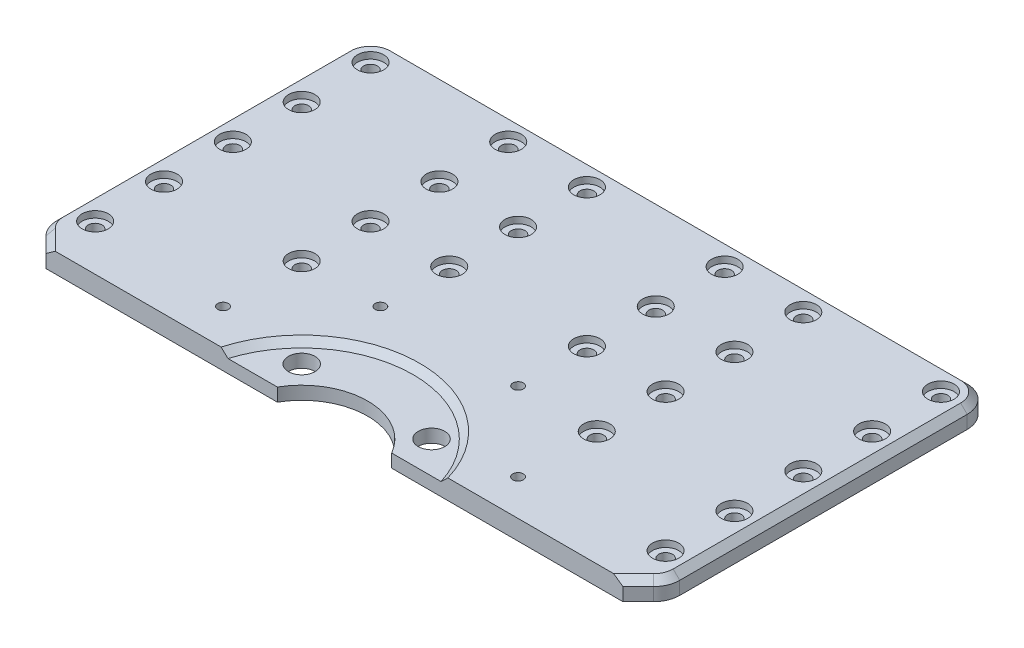
SolidWorks part; units mm, degrees
material "ABS"
ref_plane "正面" through (0, 0, 0) normal (0, 0, 1) x (1, 0, 0)
ref_plane "平面" through (0, 0, 0) normal (0, 1, 0) x (1, 0, 0)
ref_plane "右側面" through (0, 0, 0) normal (1, 0, 0) x (0, 0, -1)
sketch "ｽｹｯﾁ1" plane through (0, 0, 0) normal (0, 1, 0) x (1, 0, 0)
  line L0 (-10.05, 0) -> (-39, 0)
  line L1 (-39, 0) -> (-47.5, 8.5)
  line L2 (-47.5, 8.5) -> (-47.5, 58)
  line L3 (-47.5, 58) -> (47.5, 58)
  line L4 (47.5, 58) -> (47.5, 8.5)
  line L5 (47.5, 8.5) -> (39, 0)
  line L6 (39, 0) -> (10.05, 0)
  line L7 (-10.05, 0) -> (0, 0) construction
  line L8 (0, 0) -> (10.05, 0) construction
  arc A0 (10.05, 0) -> (-10.05, 0) centre (0, 0) ccw
  dimension "D1" = 20.1
  dimension "D2" = 95
  dimension "D3" = 58
  dimension "D4" = 78
extrude "ﾎﾞｽ - 押し出し1" add sketch "ｽｹｯﾁ1" along normal blind 3
hole_wizard "M2 なべ頭ねじ用座ぐり穴1" positions "ｽｹｯﾁ2" profile "ｽｹｯﾁ3" counterbore size "M2" standard "ISO"
sketch "ｽｹｯﾁ2" plane through (0, 3, 0) normal (0, 1, 0) x (1, 0, 0)
  line L0 (-43.5, 54) -> (-22.5, 54) construction
  line L2 (47.5, 58) -> (-47.5, 58) construction
  line L3 (-47.5, 58) -> (-47.5, 8.5) construction
  point P0 (-43.5, 54)
  point P2 (-22.5, 54)
  dimension "D1" = 4
  dimension "D2" = 4
  dimension "D3" = 21
sketch "ｽｹｯﾁ3" plane through (-43.5, 3, -54) normal (1, 0, 0) x (0, 0, 1)
  line L0 (0, 0) -> (0, 4.6309)
  line L1 (0, 4.6309) -> (1.05, 4)
  line L2 (1.05, 4) -> (1.05, 1)
  line L3 (1.05, 1) -> (2, 1)
  line L4 (2, 1) -> (2, 0)
  line L5 (2, 0) -> (0, 0)
  line L10 (0, 4.6309) -> (-1.05, 4) construction
  line L11 (0, -6.35) -> (0, 107.95) construction
  dimension "穴の直径" = 2.1
  dimension "穴の深さ" = 4
  dimension "座ぐり穴の直径" = 4
  dimension "座ぐり穴の深さ" = 1
  dimension "ﾄﾞﾘﾙ角度" = 118
pattern_linear "直線ﾊﾟﾀｰﾝ1" count 3 spacing 33 along (1, 0, 0) of "M2 なべ頭ねじ用座ぐり穴1"
pattern_linear "直線ﾊﾟﾀｰﾝ2" count 3 spacing 10.5 along (0, 0, 1) of "M2 なべ頭ねじ用座ぐり穴1", "直線ﾊﾟﾀｰﾝ1"
pattern_linear "直線ﾊﾟﾀｰﾝ3" count 2 spacing 31.5 along (0, 0, 1) of "M2 なべ頭ねじ用座ぐり穴1"
hole_wizard "M2 ねじ穴1" positions "ｽｹｯﾁ4" profile "ｽｹｯﾁ5" tap size "M2" standard "ISO"
sketch "ｽｹｯﾁ4" plane through (0, 3, 0) normal (0, 1, 0) x (1, 0, 0)
  line L0 (-22.5, 10.5) -> (-22.5, 22.5) construction
  line L1 (-22.5, 22.5) -> (-10.5, 22.5) construction
  line L2 (-10.5, 22.5) -> (-10.5, 33) construction
  line L4 (-39, 0) -> (-10.05, 0) construction
  point P0 (-10.5, 22.5)
  point P2 (-22.5, 10.5)
  dimension "D1" = 10.5
sketch "ｽｹｯﾁ5" plane through (-10.5, 3, -22.5) normal (1, 0, 0) x (0, 0, 1)
  line L0 (0, 0) -> (0, 6.4807)
  line L1 (0, 6.4807) -> (0.8, 6)
  line L2 (0.8, 6) -> (0.8, 0)
  line L5 (0.8, 0) -> (0, 0)
  line L10 (0, 6.4807) -> (-0.8, 6) construction
  line L11 (0, -6.35) -> (0, 107.95) construction
  dimension "ねじ下穴ﾄﾞﾘﾙ直径" = 1.6
  dimension "ねじ下穴ﾄﾞﾘﾙの深さ" = 6
  dimension "ﾄﾞﾘﾙ角度" = 118
cosmetic thread "穴のねじ山1" parameters "D1"=4, "D2"=2
cosmetic thread "穴のねじ山2" parameters "D1"=4, "D2"=2
hole_wizard "M2 なべ頭ねじ用座ぐり穴2" positions "ｽｹｯﾁ6" profile "ｽｹｯﾁ7" counterbore size "M2" standard "ISO"
sketch "ｽｹｯﾁ6" plane through (0, 3, 0) normal (0, 1, 0) x (1, 0, 0)
  line L0 (-43.5, 22.5) -> (-43.5, 12) construction
  line L3 (-43.5, 33) -> (-43.5, 22.5) construction
  point P0 (-43.5, 12)
sketch "ｽｹｯﾁ7" plane through (-43.5, 3, -12) normal (1, 0, 0) x (0, 0, 1)
  line L0 (0, 0) -> (0, 6.6309)
  line L1 (0, 6.6309) -> (1.05, 6)
  line L2 (1.05, 6) -> (1.05, 1)
  line L3 (1.05, 1) -> (2, 1)
  line L4 (2, 1) -> (2, 0)
  line L5 (2, 0) -> (0, 0)
  line L10 (0, 6.6309) -> (-1.05, 6) construction
  line L11 (0, -6.35) -> (0, 107.95) construction
  dimension "穴の直径" = 2.1
  dimension "穴の深さ" = 6
  dimension "座ぐり穴の直径" = 4
  dimension "座ぐり穴の深さ" = 1
  dimension "ﾄﾞﾘﾙ角度" = 118
mirror "ﾐﾗｰ1" about plane through (0, 0, 0) normal (1, 0, 0) of "M2 なべ頭ねじ用座ぐり穴2", "M2 ねじ穴1", "直線ﾊﾟﾀｰﾝ3"
cosmetic thread "穴のねじ山3" parameters "D1"=4, "D2"=2
cosmetic thread "穴のねじ山4" parameters "D1"=4, "D2"=2
sketch "ｽｹｯﾁ8" plane through (0, 3, 0) normal (0, 1, 0) x (1, 0, 0)
  circle A0 centre (0, 0) radius 17
  dimension "D1" = 34
extrude "ｶｯﾄ - 押し出し1" cut sketch "ｽｹｯﾁ8" against normal blind 1
sketch "ｽｹｯﾁ9" plane through (0, 2, 0) normal (0, 1, 0) x (1, 0, 0)
  line L0 (-9.8995, 9.8995) -> (0, 0) construction
  line L2 (-17, 0) -> (-10.05, 0) construction
  circle A0 centre (-9.8995, 9.8995) radius 2.025
  dimension "D1" = 4.05
  dimension "D2" = 45
  dimension "D3" = 14
extrude "ｶｯﾄ - 押し出し2" cut sketch "ｽｹｯﾁ9" against normal through all
pattern_circular "円形ﾊﾟﾀｰﾝ1" count 2 every 90 about axis through (0, 3, 0) along (0, -1, 0) of "ｶｯﾄ - 押し出し2"
fillet "ﾌｨﾚｯﾄ1" radius 4 6 edges at (-47.5, 1.5, -8.5) (-39, 1.5, 0) (39, 1.5, 0) (47.5, 1.5, -8.5) (47.5, 1.5, -58) (-47.5, 1.5, -58)
chamfer "面取り1" distance 1 angle 45 14 edges at (0, 3, -17) (27.1716, 3, 0) (38.8739, 3, -0.3045) (43.25, 3, -4.25) (47.1955, 3, -8.6261) (47.5, 3, -32.0784) (-27.1716, 3, 0) (46.3284, 3, -56.8284) (-38.8739, 3, -0.3045) (0, 3, -58) (-43.25, 3, -4.25) (-46.3284, 3, -56.8284) (-47.1955, 3, -8.6261) (-47.5, 3, -32.0784)
sketch "ｽｹｯﾁ11" plane through (0, 3, 0) normal (0, 1, 0) x (1, 0, 0)
  line L0 (-17, 0) -> (-37.3431, 0) construction
  line L1 (-47.5, 5) -> (47.5, 5)
  line L2 (-47.5, 5) -> (-47.5, -5)
  line L3 (-47.5, -5) -> (47.5, -5)
  line L4 (47.5, 5) -> (47.5, -5)
  line L5 (-47.5, 5) -> (47.5, -5) construction
  line L6 (-47.5, -5) -> (47.5, 5) construction
  line L7 (-47.5, 10.1569) -> (-47.5, 54) construction
  point P4 (0, 0)
  dimension "D2" = 5
extrude "ｶｯﾄ - 押し出し3" cut sketch "ｽｹｯﾁ11" against normal through all
